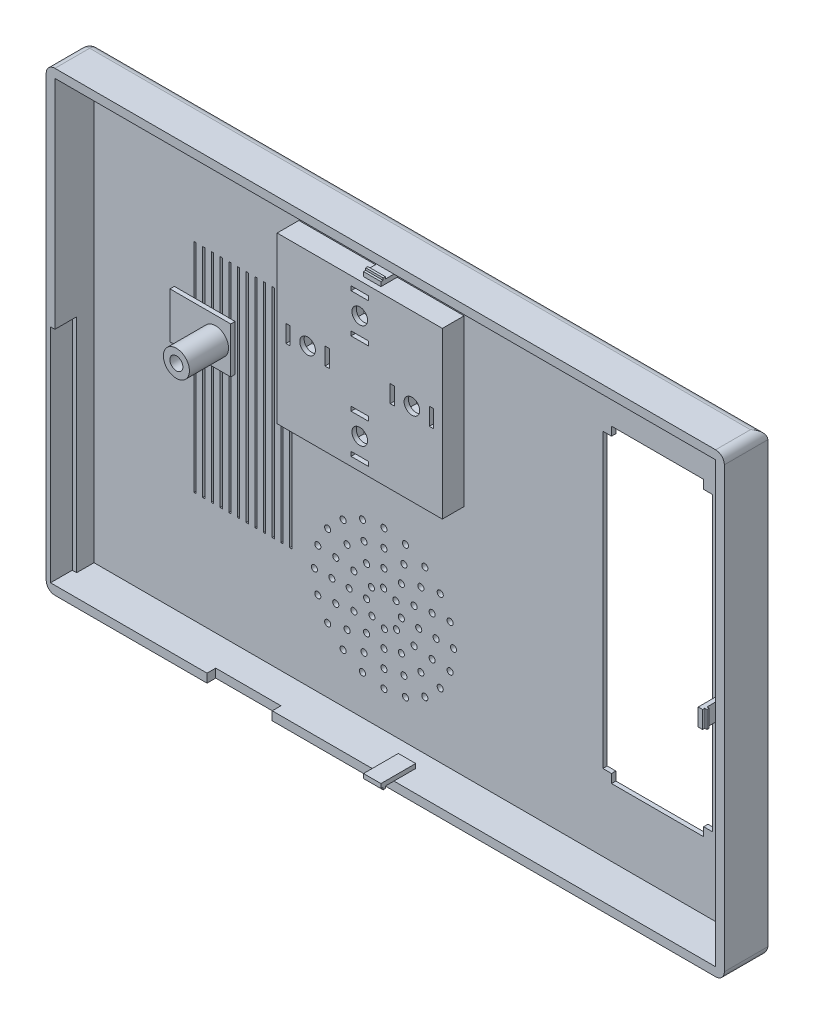
SolidWorks part; units mm, degrees
material "ABS"
ref_plane "Front Plane" through (0, 0, 0) normal (0, 0, 1) x (1, 0, 0)
ref_plane "Top Plane" through (0, 0, 0) normal (0, 1, 0) x (1, 0, 0)
ref_plane "Right Plane" through (0, 0, 0) normal (1, 0, 0) x (0, 0, -1)
sketch "Sketch2" plane through (0, 0, 0) normal (0, 0, 1) x (1, 0, 0)
  line L1 (0, 0) -> (156, 0)
  line L2 (0, 0) -> (0, 105)
  line L3 (0, 105) -> (156, 105)
  line L4 (156, 0) -> (156, 105)
  dimension "D1" = 105
  dimension "D2" = 156
extrude "Boss-Extrude1" add sketch "Sketch2" along normal blind 10
shell "Shell1" thickness 2 removed face at (78, 52.5, 10)
sketch "Sketch3" plane through (0, 0, 0) normal (0, 0, -1) x (-1, 0, 0)
  line L0 (0, 0) -> (-156, 0) construction
  line L1 (-144.25, 86.73) -> (-119.05, 86.73)
  line L2 (-144.25, 86.73) -> (-144.25, 19.53)
  line L3 (-144.25, 19.53) -> (-119.05, 19.53)
  line L4 (-119.05, 86.73) -> (-119.05, 19.53)
  line L8 (-156, 0) -> (-156, 105) construction
  dimension "D1" = 25.2
  dimension "D2" = 19.53
  dimension "D3" = 67.2
  dimension "D4" = 11.75
extrude "Cut-Extrude1" cut sketch "Sketch3" against normal blind 1
sketch "Sketch4" plane through (0, 0, 0) normal (0, 0, -1) x (-1, 0, 0)
  line L0 (-119.05, 86.73) -> (-144.25, 86.73) construction
  line L1 (-142.25, 86.73) -> (-121.05, 86.73)
  line L2 (-142.25, 86.73) -> (-142.25, 88.73)
  line L3 (-142.25, 88.73) -> (-121.05, 88.73)
  line L4 (-121.05, 86.73) -> (-121.05, 88.73)
  line L5 (-119.05, 19.53) -> (-119.05, 86.73) construction
  dimension "D1" = 2
  dimension "D2" = 21.2
  dimension "D3" = 2
extrude "Cut-Extrude2" cut sketch "Sketch4" against normal blind 1
sketch "Sketch5" plane through (0, 0, 0) normal (0, 0, -1) x (-1, 0, 0)
  line L0 (-144.25, 19.53) -> (-119.05, 19.53) construction
  line L1 (-142.25, 19.53) -> (-121.05, 19.53)
  line L2 (-142.25, 19.53) -> (-142.25, 17.53)
  line L3 (-142.25, 17.53) -> (-121.05, 17.53)
  line L4 (-121.05, 19.53) -> (-121.05, 17.53)
  line L5 (-119.05, 19.53) -> (-119.05, 86.73) construction
  dimension "D1" = 2
  dimension "D2" = 21.2
  dimension "D3" = 2
extrude "Cut-Extrude3" cut sketch "Sketch5" against normal blind 1
sketch "Sketch9" plane through (0, 0, 0) normal (0, 0, -1) x (-1, 0, 0)
  line L0 (-156, 105) -> (0, 105) construction
  line L1 (-87.13, 93.75) -> (-49.13, 93.75)
  line L2 (-87.13, 93.75) -> (-87.13, 55.75)
  line L3 (-87.13, 55.75) -> (-49.13, 55.75)
  line L4 (-49.13, 93.75) -> (-49.13, 55.75)
  line L5 (-156, 0) -> (-156, 105) construction
  dimension "D1" = 38
  dimension "D2" = 38
  dimension "D3" = 11.25
  dimension "D4" = 68.87
extrude "Boss-Extrude5" add sketch "Sketch9" against normal blind 6
sketch "Sketch10" plane through (0, 0, 0) normal (0, 0, -1) x (-1, 0, 0)
  line L0 (-156, 105) -> (0, 105) construction
  line L1 (-85.13, 79.75) -> (-75.13, 79.75)
  line L2 (-85.13, 79.75) -> (-85.13, 69.75)
  line L3 (-85.13, 69.75) -> (-75.13, 69.75)
  line L4 (-75.13, 79.75) -> (-75.13, 69.75)
  line L5 (-156, 0) -> (-156, 105) construction
  dimension "D1" = 10
  dimension "D2" = 10
  dimension "D3" = 25.25
  dimension "D4" = 70.87
extrude "Cut-Extrude4" cut sketch "Sketch10" against normal blind 5
ref_plane "Plane4" through (68.13, 0, 0) normal (1, 0, 0) x (0, 0, -1)
mirror "Mirror3" about plane through (68.13, 0, 0) normal (1, 0, 0) of "Cut-Extrude4"
ref_plane "Plane5" through (0, 74.75, 0) normal (0, -1, 0) x (-1, 0, 0)
sketch "Sketch11" plane through (0, 0, 0) normal (0, 0, -1) x (-1, 0, 0)
  line L1 (-73.13, 91.75) -> (-63.13, 91.75)
  line L2 (-73.13, 91.75) -> (-73.13, 81.75)
  line L3 (-73.13, 81.75) -> (-63.13, 81.75)
  line L4 (-63.13, 91.75) -> (-63.13, 81.75)
  line L6 (-156, 0) -> (-156, 105) construction
  line L7 (-156, 105) -> (0, 105) construction
  dimension "D1" = 10
  dimension "D2" = 10
  dimension "D3" = 82.87
  dimension "D4" = 13.25
extrude "Cut-Extrude5" cut sketch "Sketch11" against normal blind 5
mirror "Mirror4" about plane through (0, 74.75, 0) normal (0, -1, 0) of "Cut-Extrude5"
sketch "Sketch12" plane through (0, 0, 5) normal (0, 0, -1) x (-1, 0, 0)
  line L0 (-156, 105) -> (0, 105) construction
  line L1 (-156, 0) -> (-156, 105) construction
  circle A0 centre (-68.13, 86.75) radius 1.8
  dimension "D1" = 18.25
  dimension "D2" = 87.87
extrude "Cut-Extrude6" cut sketch "Sketch12" against normal blind 1
mirror "Mirror5" about plane through (0, 74.75, 0) normal (0, -1, 0) of "Cut-Extrude6"
sketch "Sketch13" plane through (0, 0, 5) normal (0, 0, -1) x (-1, 0, 0)
  line L0 (-156, 0) -> (-156, 105) construction
  line L1 (-156, 105) -> (0, 105) construction
  circle A0 centre (-80.13, 74.75) radius 1.8
  dimension "D1" = 75.87
  dimension "D2" = 30.25
extrude "Cut-Extrude7" cut sketch "Sketch13" against normal blind 1
mirror "Mirror6" about plane through (68.13, 0, 0) normal (1, 0, 0) of "Cut-Extrude7"
ref_axis "Axis2" through (0, 52.5, 0) along (1, 0, 0)
sketch "Sketch20" plane through (0, 0, 0) normal (0, 0, -1) x (-1, 0, 0)
  line L1 (-25, 77.5) -> (-25.5, 77.5)
  line L2 (-25, 77.5) -> (-25, 27.5)
  line L3 (-25, 27.5) -> (-25.5, 27.5)
  line L4 (-25.5, 77.5) -> (-25.5, 27.5)
  line L5 (0, 105) -> (0, 0) construction
  line L6 (0, 52.5) -> (-22.1785, 52.5) construction
  point P8 (-25.25, 77.5)
  dimension "D1" = 25
  dimension "D2" = 0.5
  dimension "D3" = 25
  dimension "D4" = 25
extrude "Cut-Extrude13" cut sketch "Sketch20" against normal blind 1
pattern_linear "LPattern1" count 12 spacing 2 along (1, 0, 0) of "Cut-Extrude13"
ref_plane "Plane6" through (0, 52.5, 0) normal (0, 1, 0) x (1, 0, 0)
ref_plane "Plane7" through (78, 0, 0) normal (-1, 0, 0) x (0, 0, 1)
sketch "Sketch27" plane through (0, 0, 0) normal (0, 0, -1) x (-1, 0, 0)
  line L0 (-156, 0) -> (-156, 105) construction
  line L1 (0, 0) -> (-156, 0) construction
  circle A0 centre (-68.7, 26.25) radius 8
  dimension "D1" = 87.3
  dimension "D2" = 26.25
ref_axis "Axis3" through (68.7, 26.25, 0) along (0, 0, 1)
sketch "Sketch28" plane through (0, 0, 0) normal (0, 0, -1) x (-1, 0, 0)
  circle A0 centre (-68.7, 34.25) radius 0.7
  circle A1 centre (-68.7, 26.25) radius 8 construction
extrude "Cut-Extrude15" cut sketch "Sketch28" against normal blind 1
pattern_circular "CirPattern1" count 12 over 360 about axis through (68.7, 26.25, 0) along (0, 0, 1) of "Cut-Extrude15"
sketch "Sketch29" plane through (0, 0, 0) normal (0, 0, -1) x (-1, 0, 0)
  circle A0 centre (-68.6123, 30.25) radius 0.7
  dimension "D1" = 4
extrude "Cut-Extrude16" cut sketch "Sketch29" against normal blind 1
pattern_circular "CirPattern2" count 8 over 360 about axis through (68.7, 26.25, 0) along (0, 0, 1) of "Cut-Extrude16"
sketch "Sketch30" plane through (0, 0, 0) normal (0, 0, -1) x (-1, 0, 0)
  circle A0 centre (-68.7, 38.25) radius 0.7
  dimension "D1" = 12
  dimension "D2" = 1.4
extrude "Cut-Extrude17" cut sketch "Sketch30" against normal blind 1
pattern_circular "CirPattern3" count 16 over 360 about axis through (68.7, 26.25, 0) along (0, 0, 1) of "Cut-Extrude17"
sketch "Sketch31" plane through (0, 0, 0) normal (0, 0, -1) x (-1, 0, 0)
  circle A0 centre (-68.7, 42.25) radius 0.7
  dimension "D1" = 16
  dimension "D2" = 1.4
extrude "Cut-Extrude18" cut sketch "Sketch31" against normal blind 1
pattern_circular "CirPattern4" count 20 over 360 about axis through (68.7, 26.25, 0) along (0, 0, 1) of "Cut-Extrude18"
sketch "Sketch33" plane through (0, 0, 10) normal (0, 0, 1) x (1, 0, 0)
  line L1 (2, 2) -> (1, 2)
  line L2 (2, 2) -> (2, 53)
  line L3 (2, 53) -> (1, 53)
  line L4 (1, 2) -> (1, 53)
  dimension "D1" = 1
  dimension "D2" = 51
extrude "Cut-Extrude19" cut sketch "Sketch33" against normal blind 5
sketch "Sketch34" plane through (0, 2, 0) normal (0, 1, 0) x (1, 0, 0)
  line L1 (76, -5) -> (80, -5)
  line L2 (76, -5) -> (76, -13)
  line L3 (76, -13) -> (80, -13)
  line L4 (80, -5) -> (80, -13)
  line L5 (1, -10) -> (154, -10) construction
  line L6 (78, 5.5) -> (78, -5.5) construction
  dimension "D1" = 8
  dimension "D2" = 5
  dimension "D3" = 2
  dimension "D4" = 2
extrude "Boss-Extrude9" add sketch "Sketch34" along normal blind 1
sketch "Sketch35" plane through (0, 2, 0) normal (0, -1, 0) x (1, 0, 0)
  line L0 (76, 10) -> (76, 13) construction
  line L1 (76, 12.5) -> (80, 12.5)
  line L2 (76, 12.5) -> (76, 12)
  line L3 (76, 12) -> (80, 12)
  line L4 (80, 12.5) -> (80, 12)
  line L5 (80, 13) -> (80, 10) construction
  line L6 (76, 13) -> (80, 13) construction
  dimension "D1" = 0.5
  dimension "D2" = 0.5
extrude "Boss-Extrude10" add sketch "Sketch35" along normal blind 0.5
mirror "Mirror9" about plane through (0, 52.5, 0) normal (0, 1, 0) of "Boss-Extrude9", "Boss-Extrude10"
sketch "Sketch36" plane through (154, 0, 0) normal (-1, 0, 0) x (0, 0, 1)
  line L0 (10, 2) -> (10, 103) construction
  line L1 (5, 54.7622) -> (13, 54.7622)
  line L2 (5, 54.7622) -> (5, 50.7622)
  line L3 (5, 50.7622) -> (13, 50.7622)
  line L4 (13, 54.7622) -> (13, 50.7622)
  dimension "D1" = 4
  dimension "D2" = 8
  dimension "D3" = 5
extrude "Boss-Extrude11" add sketch "Sketch36" along normal blind 1
sketch "Sketch37" plane through (154, 0, 0) normal (1, 0, 0) x (0, 0, -1)
  line L0 (-13, 54.7622) -> (-10, 54.7622) construction
  line L1 (-12.5, 54.7622) -> (-12, 54.7622)
  line L2 (-12.5, 54.7622) -> (-12.5, 50.7622)
  line L3 (-12.5, 50.7622) -> (-12, 50.7622)
  line L4 (-12, 54.7622) -> (-12, 50.7622)
  line L5 (-10, 50.7622) -> (-13, 50.7622) construction
  line L6 (-13, 50.7622) -> (-13, 54.7622) construction
  dimension "D1" = 0.5
  dimension "D2" = 0.5
extrude "Boss-Extrude12" add sketch "Sketch37" along normal blind 0.5
sketch "Sketch38" plane through (0, 0, 0) normal (0, -1, 0) x (1, 0, 0)
  line L0 (0, 10) -> (156, 10) construction
  line L1 (37, 10) -> (52, 10)
  line L2 (37, 10) -> (37, 8)
  line L3 (37, 8) -> (52, 8)
  line L4 (52, 10) -> (52, 8)
  dimension "D1" = 2
  dimension "D2" = 15
  dimension "D3" = 37
extrude "Cut-Extrude20" cut sketch "Sketch38" against normal blind 2
sketch "Sketch39" plane through (0, 0, 5) normal (0, 0, -1) x (-1, 0, 0)
  line L0 (-63.13, 91.75) -> (-73.13, 91.75) construction
  line L1 (-70.13, 91.75) -> (-66.13, 91.75)
  line L2 (-70.13, 91.75) -> (-70.13, 90.75)
  line L3 (-70.13, 90.75) -> (-66.13, 90.75)
  line L4 (-66.13, 91.75) -> (-66.13, 90.75)
  line L5 (-68.13, 2.75) -> (-68.13, -2.75) construction
  dimension "D1" = 4
  dimension "D2" = 1
  dimension "D3" = 2
extrude "Cut-Extrude21" cut sketch "Sketch39" against normal blind 1
sketch "Sketch41" plane through (0, 0, 5) normal (0, 0, -1) x (-1, 0, 0)
  line L0 (-85.13, 79.75) -> (-85.13, 69.75) construction
  line L1 (-85.13, 76.75) -> (-84.13, 76.75)
  line L2 (-85.13, 76.75) -> (-85.13, 72.75)
  line L3 (-85.13, 72.75) -> (-84.13, 72.75)
  line L4 (-84.13, 76.75) -> (-84.13, 72.75)
  line L5 (-2.75, 74.75) -> (2.75, 74.75) construction
  dimension "D1" = 4
  dimension "D2" = 2
  dimension "D3" = 1
extrude "Cut-Extrude22" cut sketch "Sketch41" against normal blind 1
ref_plane "Plane8" through (0, 86.75, 0) normal (0, -1, 0) x (-1, 0, 0)
ref_plane "Plane9" through (80.13, 0, 0) normal (-1, 0, 0) x (0, 0, 1)
mirror "Mirror10" about plane through (80.13, 0, 0) normal (-1, 0, 0) of "Cut-Extrude22"
mirror "Mirror11" about plane through (0, 86.75, 0) normal (0, -1, 0) of "Cut-Extrude21"
mirror "Mirror12" about plane through (0, 74.75, 0) normal (0, -1, 0) of "Mirror11"
mirror "Mirror14" about plane through (68.13, 0, 0) normal (1, 0, 0) of "Mirror10"
sketch "Sketch44" plane through (0, 0, 1) normal (0, 0, 1) x (1, 0, 0)
  line L0 (156, 105) -> (0, 105) construction
  line L1 (2, 103) -> (2, 2) construction
  circle A0 centre (30.95, 61.2) radius 3
  dimension "D1" = 43.8
  dimension "D2" = 28.95
sketch "Sketch47" plane through (0, 0, 1) normal (0, 0, 1) x (1, 0, 0)
  line L1 (20.4763, 66.2965) -> (34.4522, 66.2965)
  line L2 (20.4763, 66.2965) -> (20.4763, 55.737)
  line L3 (20.4763, 55.737) -> (34.4522, 55.737)
  line L4 (34.4522, 66.2965) -> (34.4522, 55.737)
extrude "Boss-Extrude17" add sketch "Sketch47" along normal blind 1
extrude "Boss-Extrude18" add sketch "Sketch44" along normal blind 10
sketch "Sketch48" plane through (0, 0, 11) normal (0, 0, 1) x (1, 0, 0)
  circle A0 centre (30.95, 61.2) radius 1.5
extrude "Cut-Extrude23" cut sketch "Sketch48" against normal blind 5
fillet "Fillet1" radius 2 8 edges at (0, 0, 5) (156, 0, 5) (156, 105, 5) (0, 105, 5) (0, 52.5, 0) (78, 105, 0) (154, 52.5, 1) (78, 0, 0)
sketch "Sketch49" plane through (0, 0, 0) normal (0, 0, -1) x (-1, 0, 0)
  line L0 (-86.2143, 79.75) -> (-86.2143, 69.75) construction
  line L1 (-48.4247, 79.75) -> (-48.4247, 69.75) construction
  line L2 (-66.5221, 57.2029) -> (-66.5221, 45.0687) construction
  line L3 (-66.5221, 92.3576) -> (-66.5221, 102.481) construction
  text T0 "Up" font "Century Gothic" height in points 8
  text T1 "Down" font "Century Gothic" height in points 8
  text T2 "Back" font "Century Gothic" height in points 8
  text T3 "Select" font "Century Gothic" height in points 8
extrude "Cut-Extrude24" cut sketch "Sketch49" against normal blind 0.5
